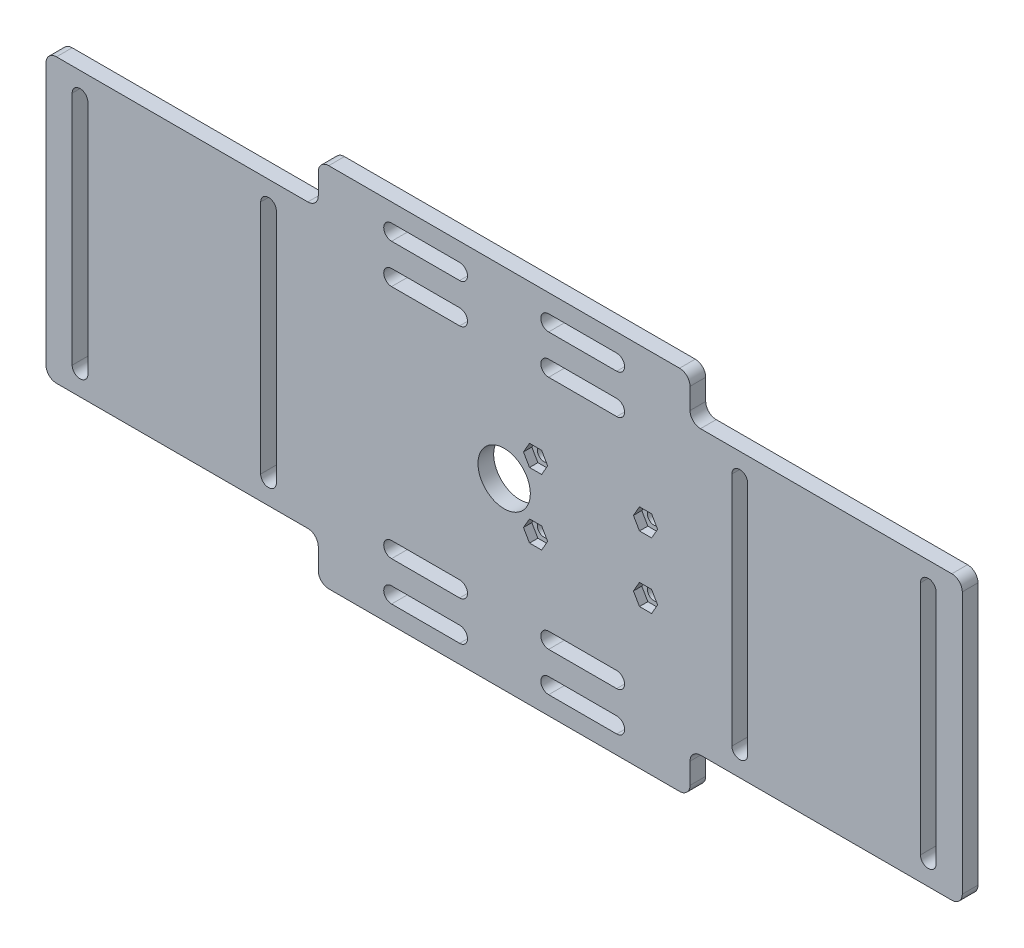
SolidWorks part; units mm, degrees
ref_plane "前基準面" through (0, 0, 0) normal (0, 0, 1) x (1, 0, 0)
ref_plane "上基準面" through (0, 0, 0) normal (0, 1, 0) x (1, 0, 0)
ref_plane "右基準面" through (0, 0, 0) normal (1, 0, 0) x (0, 0, -1)
sketch "草圖1" plane through (0, 0, 0) normal (0, 0, 1) x (1, 0, 0)
  line L0 (35.5, 33) -> (35.5, 29)
  line L1 (-33.5, 35) -> (33.5, 35)
  line L2 (-87.5, 25) -> (-87.5, -25)
  line L3 (-33.5, -35) -> (33.5, -35)
  line L4 (87.5, 25) -> (87.5, -25)
  line L5 (-87.5, 35) -> (87.5, -35) construction
  line L6 (-87.5, -35) -> (87.5, 35) construction
  line L7 (37.5, 27) -> (85.5, 27)
  line L8 (0, 71.4811) -> (0, -70.0061) construction
  line L9 (-113.0104, 0) -> (128.372, 0) construction
  line L10 (-37.5, 27) -> (-85.5, 27)
  line L11 (-35.5, 33) -> (-35.5, 29)
  line L12 (37.5, -27) -> (85.5, -27)
  line L13 (35.5, -33) -> (35.5, -29)
  line L14 (-35.5, -33) -> (-35.5, -29)
  line L15 (-37.5, -27) -> (-85.5, -27)
  arc A0 (35.5, 33) -> (33.5, 35) centre (33.5, 33) ccw
  arc A1 (37.5, 27) -> (35.5, 29) centre (37.5, 29) cw
  arc A2 (87.5, 25) -> (85.5, 27) centre (85.5, 25) ccw
  arc A3 (-87.5, 25) -> (-85.5, 27) centre (-85.5, 25) cw
  arc A4 (-37.5, 27) -> (-35.5, 29) centre (-37.5, 29) ccw
  arc A5 (-35.5, 33) -> (-33.5, 35) centre (-33.5, 33) cw
  arc A6 (87.5, -25) -> (85.5, -27) centre (85.5, -25) cw
  arc A7 (37.5, -27) -> (35.5, -29) centre (37.5, -29) ccw
  arc A8 (35.5, -33) -> (33.5, -35) centre (33.5, -33) cw
  arc A9 (-35.5, -33) -> (-33.5, -35) centre (-33.5, -33) ccw
  arc A10 (-37.5, -27) -> (-35.5, -29) centre (-37.5, -29) cw
  arc A11 (-87.5, -25) -> (-85.5, -27) centre (-85.5, -25) ccw
  point P0 (0, 0)
  point P13 (35.5, 27)
  point P29 (-35.5, 27)
  point P39 (35.5, -27)
  point P49 (-35.5, -27)
  dimension "D1" = 2
  dimension "D2" = 2
  dimension "D3" = 2
  dimension "D4" = 175
  dimension "D5" = 70
  dimension "D6" = 8
  dimension "D7" = 52
extrude "填料-伸長1" add sketch "草圖1" along normal blind 3
sketch "草圖2" plane through (0, 0, 3) normal (0, 0, 1) x (1, 0, 0)
  line L0 (-1000, 0) -> (49000, 0) construction
  line L1 (45, -986.1952) -> (45, 49013.8048) construction
  line L2 (-81, -962.7943) -> (-81, 49037.2057) construction
  line L3 (45, -22.5) -> (45, 22.5) construction
  line L4 (43.5, -22.5) -> (43.5, 22.5)
  line L5 (46.5, -22.5) -> (46.5, 22.5)
  line L6 (-45, -1000) -> (-45, 49000) construction
  line L7 (-45, -22.5) -> (-45, 22.5) construction
  line L8 (-46.5, -22.5) -> (-46.5, 22.5)
  line L9 (-43.5, -22.5) -> (-43.5, 22.5)
  line L10 (0, -1000) -> (0, 49000) construction
  line L11 (-1010.5287, 30) -> (48989.4713, 30) construction
  line L12 (-1007.193, -30) -> (48992.807, -30) construction
  line L13 (21.5, -30) -> (8.5, -30) construction
  line L16 (6, -996.0597) -> (6, 49003.9403) construction
  line L19 (81, -968.4295) -> (81, 49031.5705) construction
  line L20 (-81, -22.5) -> (-81, 22.5) construction
  line L21 (-82.5, -22.5) -> (-82.5, 22.5)
  line L22 (-79.5, -22.5) -> (-79.5, 22.5)
  line L23 (81, -22.5) -> (81, 22.5) construction
  line L24 (79.5, -22.5) -> (79.5, 22.5)
  line L25 (82.5, -22.5) -> (82.5, 22.5)
  line L26 (27, -997.4467) -> (27, 49002.5533) construction
  line L27 (-1014.4971, -6.25) -> (48985.5029, -6.25) construction
  line L28 (-1015.8254, 6.25) -> (48984.1746, 6.25) construction
  line L29 (-33.5, -35) -> (33.5, -35) construction
  line L30 (21.5, -31.5) -> (8.5, -31.5)
  line L33 (21.5, -28.5) -> (8.5, -28.5)
  line L34 (-21.5, -30) -> (-8.5, -30) construction
  line L35 (-21.5, -31.5) -> (-8.5, -31.5)
  line L36 (-21.5, -28.5) -> (-8.5, -28.5)
  line L37 (21.5, 30) -> (8.5, 30) construction
  line L38 (21.5, 31.5) -> (8.5, 31.5)
  line L39 (21.5, 28.5) -> (8.5, 28.5)
  line L40 (-21.5, 30) -> (-8.5, 30) construction
  line L41 (-21.5, 31.5) -> (-8.5, 31.5)
  line L42 (-21.5, 28.5) -> (-8.5, 28.5)
  line L43 (21.5, 22.5) -> (8.5, 22.5) construction
  line L44 (21.5, 24) -> (8.5, 24)
  line L45 (21.5, 21) -> (8.5, 21)
  line L46 (-21.5, 22.5) -> (-8.5, 22.5) construction
  line L47 (-21.5, 24) -> (-8.5, 24)
  line L48 (-21.5, 21) -> (-8.5, 21)
  line L49 (-21.5, -22.5) -> (-8.5, -22.5) construction
  line L50 (-21.5, -24) -> (-8.5, -24)
  line L51 (-21.5, -21) -> (-8.5, -21)
  line L52 (21.5, -22.5) -> (8.5, -22.5) construction
  line L53 (21.5, -24) -> (8.5, -24)
  line L54 (21.5, -21) -> (8.5, -21)
  arc A0 (43.5, -22.5) -> (46.5, -22.5) centre (45, -22.5) ccw
  arc A1 (46.5, 22.5) -> (43.5, 22.5) centre (45, 22.5) ccw
  arc A2 (-46.5, -22.5) -> (-43.5, -22.5) centre (-45, -22.5) ccw
  arc A3 (-43.5, 22.5) -> (-46.5, 22.5) centre (-45, 22.5) ccw
  arc A12 (-82.5, -22.5) -> (-79.5, -22.5) centre (-81, -22.5) ccw
  arc A13 (-79.5, 22.5) -> (-82.5, 22.5) centre (-81, 22.5) ccw
  arc A14 (79.5, -22.5) -> (82.5, -22.5) centre (81, -22.5) ccw
  arc A15 (82.5, 22.5) -> (79.5, 22.5) centre (81, 22.5) ccw
  circle A16 centre (0, 0) radius 5
  circle A17 centre (27, 6.25) radius 1.25
  circle A18 centre (6, 6.25) radius 1.25
  circle A19 centre (6, -6.25) radius 1.25
  circle A20 centre (27, -6.25) radius 1.25
  arc A23 (21.5, -31.5) -> (21.5, -28.5) centre (21.5, -30) ccw
  arc A24 (8.5, -28.5) -> (8.5, -31.5) centre (8.5, -30) ccw
  arc A25 (-21.5, -31.5) -> (-21.5, -28.5) centre (-21.5, -30) cw
  arc A26 (-8.5, -28.5) -> (-8.5, -31.5) centre (-8.5, -30) cw
  arc A27 (21.5, 31.5) -> (21.5, 28.5) centre (21.5, 30) cw
  arc A28 (8.5, 28.5) -> (8.5, 31.5) centre (8.5, 30) cw
  arc A29 (-21.5, 31.5) -> (-21.5, 28.5) centre (-21.5, 30) ccw
  arc A30 (-8.5, 28.5) -> (-8.5, 31.5) centre (-8.5, 30) ccw
  arc A31 (21.5, 24) -> (21.5, 21) centre (21.5, 22.5) cw
  arc A32 (8.5, 21) -> (8.5, 24) centre (8.5, 22.5) cw
  arc A33 (-21.5, 24) -> (-21.5, 21) centre (-21.5, 22.5) ccw
  arc A34 (-8.5, 21) -> (-8.5, 24) centre (-8.5, 22.5) ccw
  arc A35 (-21.5, -24) -> (-21.5, -21) centre (-21.5, -22.5) cw
  arc A36 (-8.5, -21) -> (-8.5, -24) centre (-8.5, -22.5) cw
  arc A37 (21.5, -24) -> (21.5, -21) centre (21.5, -22.5) ccw
  arc A38 (8.5, -21) -> (8.5, -24) centre (8.5, -22.5) ccw
  point P9 (45, 0)
  point P16 (-45, 0)
  point P31 (15, -30)
  point P47 (-81, 0)
  point P54 (81, 0)
  point P72 (-15, -30)
  point P81 (15, 30)
  point P88 (-15, 30)
  point P97 (15, 22.5)
  point P102 (-15, 22.5)
  point P110 (-15, -22.5)
  point P116 (15, -22.5)
  dimension "D10" = 1.5
  dimension "D20" = 10
  dimension "D21" = 2.5
  dimension "D27" = 7.5
  dimension "D2" = 45
  dimension "D3" = 3
  dimension "D4" = 90
  dimension "D5" = 45
  dimension "D6" = 3
  dimension "D7" = 45
  dimension "D8" = 60
  dimension "D9" = 30
  dimension "D11" = 13
  dimension "D12" = 12.5
  dimension "D13" = 21
  dimension "D14" = 162
  dimension "D15" = 81
  dimension "D16" = 3
  dimension "D17" = 45
  dimension "D18" = 45
  dimension "D19" = 3
  dimension "D22" = 28.75
  dimension "D23" = 6
  dimension "D24" = 8.5
  dimension "D25" = 2
  dimension "D28" = 7.5
  dimension "D26" = 2
extrude "除料-伸長1" cut sketch "草圖2" against normal through all
sketch "草圖3" plane through (0, 0, 3) normal (0, 0, 1) x (1, 0, 0)
  line L0 (29.3094, -6.25) -> (28.1547, -4.25)
  line L1 (8.3094, -6.25) -> (7.1547, -4.25)
  line L2 (7.1547, -4.25) -> (4.8453, -4.25)
  line L3 (4.8453, -4.25) -> (3.6906, -6.25)
  line L4 (3.6906, -6.25) -> (4.8453, -8.25)
  line L5 (4.8453, -8.25) -> (7.1547, -8.25)
  line L6 (7.1547, -8.25) -> (8.3094, -6.25)
  line L7 (28.1547, -4.25) -> (25.8453, -4.25)
  line L8 (25.8453, -4.25) -> (24.6906, -6.25)
  line L9 (24.6906, -6.25) -> (25.8453, -8.25)
  line L10 (25.8453, -8.25) -> (28.1547, -8.25)
  line L11 (28.1547, -8.25) -> (29.3094, -6.25)
  line L12 (29.3094, 6.25) -> (28.1547, 8.25)
  line L13 (28.1547, 8.25) -> (25.8453, 8.25)
  line L14 (25.8453, 8.25) -> (24.6906, 6.25)
  line L15 (24.6906, 6.25) -> (25.8453, 4.25)
  line L16 (25.8453, 4.25) -> (28.1547, 4.25)
  line L17 (28.1547, 4.25) -> (29.3094, 6.25)
  line L18 (8.3094, 6.25) -> (7.1547, 8.25)
  line L19 (7.1547, 8.25) -> (4.8453, 8.25)
  line L20 (4.8453, 8.25) -> (3.6906, 6.25)
  line L21 (3.6906, 6.25) -> (4.8453, 4.25)
  line L22 (4.8453, 4.25) -> (7.1547, 4.25)
  line L23 (7.1547, 4.25) -> (8.3094, 6.25)
  circle A0 centre (6, -6.25) radius 2 construction
  circle A3 centre (27, -6.25) radius 2 construction
  circle A4 centre (27, 6.25) radius 2 construction
  circle A5 centre (6, 6.25) radius 2 construction
  dimension "D1" = 4
  dimension "D2" = 2
  dimension "D3" = 2
extrude "除料-伸長2" cut sketch "草圖3" against normal blind 1.6
sketch "草圖4" plane through (0, 0, 0) normal (0, 0, -1) x (-1, 0, 0)
  circle A0 centre (-27, 6.25) radius 1.25
  circle A1 centre (-27, -6.25) radius 1.25
  circle A2 centre (-6, 6.25) radius 1.25
  circle A3 centre (-6, -6.25) radius 1.25
  circle A4 centre (-27, 6.25) radius 2
  circle A5 centre (-27, -6.25) radius 2
  circle A6 centre (-6, 6.25) radius 2
  circle A7 centre (-6, -6.25) radius 2
  dimension "D1" = 0.75
extrude "填料-伸長2" add sketch "草圖4" along normal blind 2
chamfer "導角1" distance 0.5 angle 30 4 edges at (25.75, 6.25, -2) (4.75, 6.25, -2) (4.75, -6.25, -2) (25.75, -6.25, -2) first distance on face at (25, 6.25, -2) first distance on face at (4, 6.25, -2) first distance on face at (4, -6.25, -2) first distance on face at (25, -6.25, -2)
